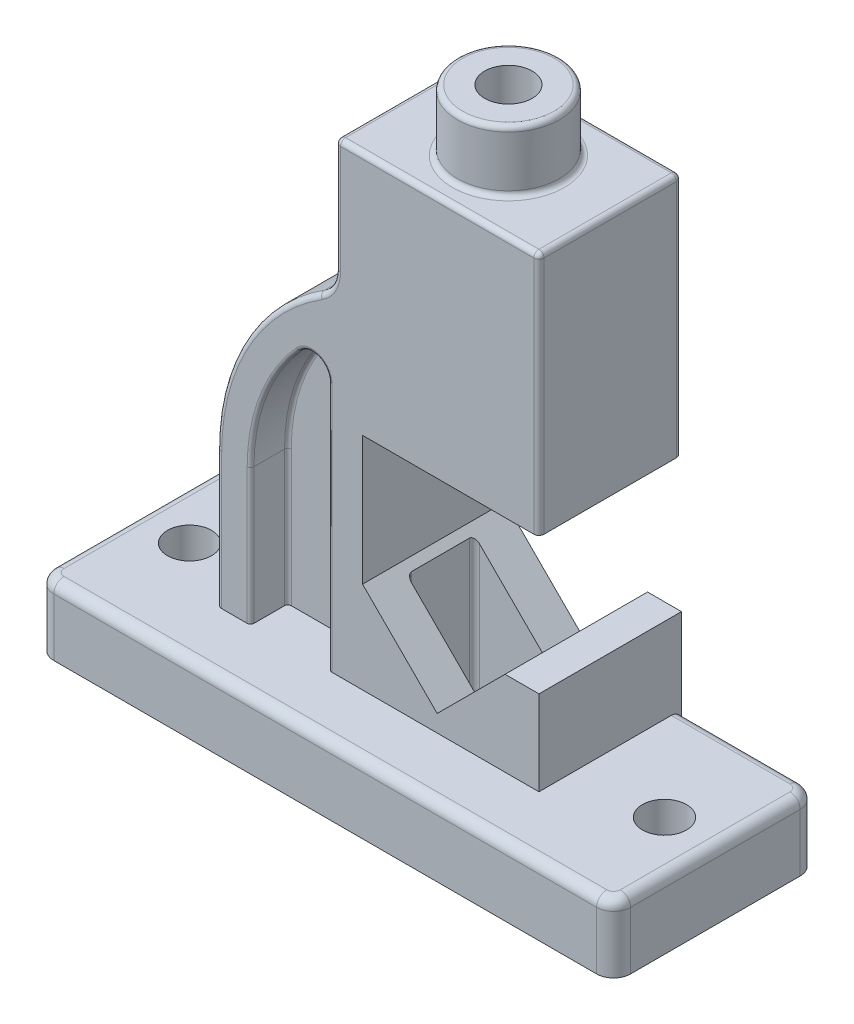
SolidWorks part; units mm, degrees
material "Stainless Steel (ferritic)"
ref_plane "Front Plane" through (0, 0, 0) normal (0, 0, 1) x (1, 0, 0)
ref_plane "Top Plane" through (0, 0, 0) normal (0, 1, 0) x (1, 0, 0)
ref_plane "Right Plane" through (0, 0, 0) normal (1, 0, 0) x (0, 0, -1)
sketch "Sketch1" plane through (0, 0, 0) normal (0, 0, 1) x (1, 0, 0)
  line L0 (0, 0) -> (0, -79948.4012) construction
  line L1 (0, 0) -> (79948.4012, 0) construction
  line L2 (30, 20) -> (30, 45)
  line L3 (-100, 0) -> (70, 0)
  line L4 (-100, 0) -> (-100, 20)
  line L5 (-100, 20) -> (70, 20)
  line L6 (70, 0) -> (70, 20)
  line L7 (30, 45) -> (20, 45)
  line L8 (20, 45) -> (0, 25)
  line L9 (0, 25) -> (-22, 47)
  line L10 (-65, 20) -> (-65, 60)
  line L11 (-22, 47) -> (-22, 85)
  line L12 (-22, 85) -> (30, 85)
  line L13 (30, 85) -> (30, 157)
  line L14 (30, 157) -> (-30, 157)
  line L15 (-30, 157) -> (-30, 123.4429)
  line L16 (-55, 20) -> (-55, 60)
  line L17 (-32, 20) -> (-32, 93.6303)
  arc A0 (-65, 60) -> (-34.6667, 114.9838) centre (0, 60) cw
  arc A1 (-55, 60) -> (-40.7, 96.9934) centre (0, 60) cw
  arc A2 (-55, 60) -> (-25.3846, 108.7916) centre (0, 60) cw construction
  arc A3 (-65, 60) -> (-30, 117.6628) centre (0, 60) cw construction
  arc A4 (-34.6667, 114.9838) -> (-30, 123.4429) centre (-40, 123.4429) ccw
  arc A5 (-32, 93.6303) -> (-40.7, 96.9934) centre (-37, 93.6303) ccw
  dimension "D12" = 65
  dimension "D15" = 10
  dimension "D16" = 5
  dimension "D1" = 170
  dimension "D2" = 70
  dimension "D3" = 20
  dimension "D4" = 25
  dimension "D5" = 40
  dimension "D6" = 72
  dimension "D7" = 60
  dimension "D8" = 22
  dimension "D9" = 45
  dimension "D10" = 10
  dimension "D11" = 60
  dimension "D14" = 10
  dimension "D13" = 10
extrude "Boss-Extrude1" add sketch "Sketch1" along normal blind 60 contours L3 L6 L5 L4 region at (-15, 10, 0)
extrude "Boss-Extrude2" add sketch "Sketch1<3>" along normal blind 42 contours A5 L17 L5 L2 L7 L8 L9 L11 L12 L13 L14 L15 A4 A0 L10 L16 A1 region at (-10.0459, 95.0555, 0)
sketch "Sketch1<3>" plane through (0, 0, 0) normal (0, 0, 1) x (1, 0, 0) same geometry as "Sketch1"
extrude "Boss-Extrude3" add sketch "Sketch1<4>" along normal blind 20 from offset 11 contours L17 A5 A1 L16 L5 region at (-42.7211, 55.6294, 0)
sketch "Sketch1<4>" plane through (0, 0, 0) normal (0, 0, 1) x (1, 0, 0) same geometry as "Sketch1"
sketch "Sketch2" plane through (0, 0, 0) normal (0, 0, 1) x (1, 0, 0)
  line L0 (-100, 0) -> (70, 0) construction
  line L1 (-20, 147) -> (20, 147)
  line L2 (-20, 147) -> (-20, 0)
  line L3 (-20, 0) -> (20, 0)
  line L4 (20, 147) -> (20, 0)
  line L5 (30, 85) -> (30, 157) construction
  line L6 (30, 157) -> (-30, 157) construction
  dimension "D1" = 40
  dimension "D2" = 10
  dimension "D3" = 10
extrude "Cut-Extrude1" cut sketch "Sketch2" along normal blind 20 from offset 11
sketch "Sketch3" plane through (0, 157, 0) normal (0, 1, 0) x (1, 0, 0)
  line L0 (30, -42) -> (30, 0) construction
  circle A0 centre (0, -21) radius 15
  point P8 (30, -21)
  dimension "D1" = 30
extrude "Boss-Extrude4" add sketch "Sketch3" along normal blind 18
hole_wizard "M16x2.0 Tapped Hole1" positions "Sketch4" profile "Sketch5" tap size "M16x2.0" standard "ANSI Metric" end condition up to next
sketch "Sketch4" plane through (0, 175, 0) normal (0, 1, 0) x (1, 0, 0)
  point P0 (0, -21)
sketch "Sketch5" plane through (0, 175, 21) normal (1, 0, 0) x (0, 0, 1)
  line L0 (0, 0) -> (0, 28)
  line L1 (0, 28) -> (7, 28)
  line L2 (7, 28) -> (7, 0)
  line L5 (7, 0) -> (0, 0)
  line L11 (0, -6.35) -> (0, 107.95) construction
  dimension "Thru Tap Drill Dia." = 14
  dimension "Thru Tap Drill Depth" = 28
cosmetic thread "Hole Thread1" parameters "D2"=16
hole_wizard "Ø1.0mm Dowel Hole1" positions "Sketch6" profile "Sketch7" hole size "Ø1.0" standard "ANSI Metric" end condition up to next
sketch "Sketch6" plane through (0, 20, 0) normal (0, 1, 0) x (1, 0, 0)
  line L0 (70, -60) -> (70, 0) construction
  line L1 (-100, -60) -> (-100, 0) construction
  point P0 (55, -30)
  point P2 (-85, -30)
  point P7 (70, -30)
  dimension "D1" = 15
  dimension "D2" = 15
sketch "Sketch7" plane through (55, 20, 30) normal (1, 0, 0) x (0, 0, 1)
  line L0 (0, 0) -> (0, 20)
  line L1 (0, 20) -> (6.5, 20)
  line L2 (6.5, 20) -> (6.5, 0)
  line L5 (6.5, 0) -> (0, 0)
  line L11 (0, -6.35) -> (0, 107.95) construction
  dimension "Thru Hole Dia." = 13
  dimension "Thru Hole Depth" = 20
fillet "Fillet1" radius 5 4 edges at (-100, 10, 0) (-100, 10, 60) (70, 10, 0) (70, 10, 60)
fillet "Fillet2" radius 3 9 edges at (-80, 20, 0) (-98.5355, 20, 1.4645) (-100, 20, 30) (-98.5355, 20, 58.5355) (-15, 20, 60) (68.5355, 20, 58.5355) (47.5, 20, 0) (68.5355, 20, 1.4645) (70, 20, 30)
fillet "Fillet3" radius 1.5 12 edges at (20, 116, 31) (0, 147, 31) (-20, 116, 31) (-20, 147, 21) (-20, 116, 11) (20, 116, 11) (0, 147, 11) (20, 147, 21) (20, 22.5, 11) (20, 22.5, 31) (-20, 22.5, 31) (-20, 22.5, 11)
fillet "Fillet4" radius 1.5 16 edges at (-65, 38.5, 0) (-56.9137, 91.398, 0) (-31.244, 118.6124, 0) (-65, 40, 42) (-56.9137, 91.398, 42) (-31.244, 118.6124, 42) (0, 175, 36) (-30, 140.2214, 0) (-30, 140.2214, 42) (0, 157, 0) (-30, 157, 21) (0, 157, 42) (30, 121, 42) (30, 121, 0) (30, 157, 21) (0, 157, 36)
fillet "Fillet5" radius 1 8 edges at (-32, 56.8152, 31) (-35.1972, 98.294, 31) (-51.3006, 79.8305, 31) (-32, 56.8152, 42) (-35.1972, 98.294, 42) (-51.3006, 79.8305, 42) (-55, 40, 31) (-55, 40, 42)
fillet "Fillet6" radius 1 12 edges at (-43.5, 20, 0) (-32, 56.8152, 11) (-35.1972, 98.294, 11) (-51.3006, 79.8305, 11) (-32, 56.8152, 0) (-35.1972, 98.294, 0) (-51.3006, 79.8305, 0) (-55, 20, 5.5) (-32, 20, 5.5) (-43.5, 20, 11) (-55, 40, 11) (-55, 40, 0)
